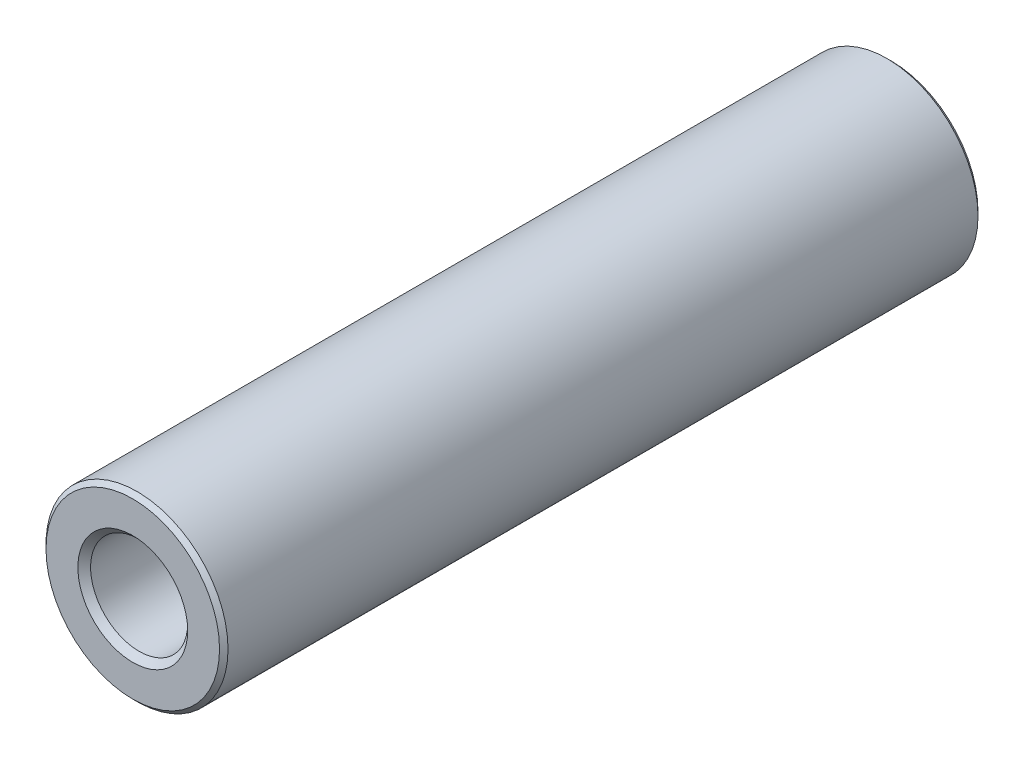
SolidWorks part; units mm, degrees
material "6061 Alloy"
ref_plane "Front Plane" through (0, 0, 0) normal (0, 0, 1) x (1, 0, 0)
ref_plane "Top Plane" through (0, 0, 0) normal (0, 1, 0) x (1, 0, 0)
ref_plane "Right Plane" through (0, 0, 0) normal (1, 0, 0) x (0, 0, -1)
sketch "Sketch1" plane through (0, 0, 0) normal (0, 0, 1) x (1, 0, 0)
  circle A0 centre (0, 0) radius 3 construction
  circle A1 centre (0, 0) radius 1.6 construction
  point P4 (0, 3)
  dimension "ID" = 3.2
  dimension "OD" = 6
sketch "Sketch2" plane through (0, 0, 0) normal (1, 0, 0) x (0, 0, -1)
  line L0 (-12.5, 3) -> (12.5, 3) construction
  dimension "Length" = 25
sketch "Sketch3" plane through (0, 0, 0) normal (0, 0, 1) x (1, 0, 0)
  circle A0 centre (0, 0) radius 1.6 construction
  circle A1 centre (0, 0) radius 3 construction
  circle A2 centre (0, 0) radius 1.6
  circle A3 centre (0, 0) radius 3
extrude "Boss-Extrude1" add sketch "Sketch3" against normal up to vertex (12.5 mm away) and the other way up to vertex (12.5 mm away) up to point (0, 3, -12.5) other way up to point (0, 3, 12.5)
chamfer "Chamfer1" distance 0.14 angle 45 2 edges at (3, 0, 12.5) (3, 0, -12.5)
chamfer "Chamfer2" distance 0.21 angle 45 2 edges at (1.6, 0, 12.5) (1.6, 0, -12.5)
equation "\"D1@Chamfer1\"=(\"OD@Sketch1\"-\"ID@Sketch1\")*0.05"
equation "\"D1@Chamfer2\"=(\"OD@Sketch1\"-\"ID@Sketch1\")*0.075"
